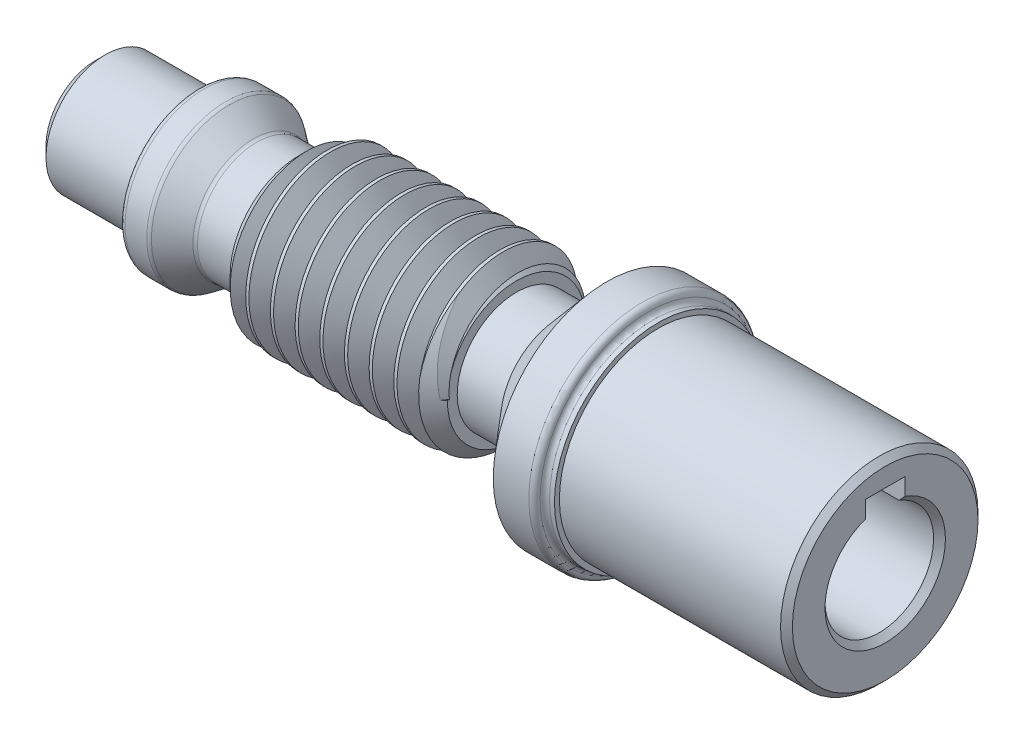
SolidWorks part; units mm, degrees
ref_plane "Horní rovina" through (0, 0, 0) normal (0, 0, 1) x (1, 0, 0)
ref_plane "Přední rovina" through (0, 0, 0) normal (0, 1, 0) x (1, 0, 0)
ref_plane "Pravá rovina" through (0, 0, 0) normal (1, 0, 0) x (0, 0, -1)
sketch "Skica1" plane through (0, 0, 0) normal (0, 0, 1) x (1, 0, 0)
  line L0 (-66.8729, 0) -> (68.6178, 0) construction
  line L1 (-40, 0) -> (40, 0)
  line L2 (40, 0) -> (40, 10)
  line L3 (40, 10) -> (17, 10)
  line L4 (17, 10) -> (17, 10.5)
  line L5 (17, 10.5) -> (16.5, 10.5)
  line L6 (16, 11) -> (16, 11.5)
  line L7 (16, 11.5) -> (11.8, 11.5)
  line L8 (11.8, 11.5) -> (7.05, 6)
  line L9 (7.05, 6) -> (2.65, 6)
  line L10 (2.65, 6) -> (2.65, 7)
  line L11 (1.15, 8.5) -> (-17.85, 8.5)
  line L12 (-19.35, 7) -> (-19.35, 6)
  line L13 (-19.35, 6) -> (-23.85, 6)
  line L14 (-23.85, 6) -> (-26.6, 8)
  line L15 (-26.6, 8) -> (-29.6, 8)
  line L16 (-40, 0) -> (-40, 6)
  line L17 (-40, 6) -> (-30.6, 6)
  line L18 (-29.6, 8) -> (-29.6, 6)
  line L19 (-17.85, 8.5) -> (-19.35, 7)
  line L20 (2.65, 7) -> (1.15, 8.5)
  arc A0 (-30.6, 6) -> (-29.6, 6) centre (-30.1, 6) ccw
  arc A1 (16.5, 10.5) -> (16, 11) centre (16.5, 11) cw
  point P6 (0, 0)
  point P13 (2.65, 8.5)
  point P16 (-19.35, 8.5)
  point P27 (16, 10.5)
  point P28 (17, 10.25)
  dimension "D4" = 0.5
  dimension "D20" = 0.5
  dimension "D22" = 0.5
  dimension "D1" = 80
  dimension "D2" = 10
  dimension "D3" = 23
  dimension "D5" = 24
  dimension "D6" = 1
  dimension "D7" = 4.2
  dimension "D8" = 4.4
  dimension "D9" = 22
  dimension "D10" = 4.5
  dimension "D11" = 46.6
  dimension "D12" = 4.75
  dimension "D13" = 6
  dimension "D14" = 8.5
  dimension "D15" = 6
  dimension "D16" = 8
  dimension "D17" = 3
  dimension "D18" = 6
  dimension "D21" = 2
  dimension "D23" = 10.4
revolve "Rotovat1" add sketch "Skica1" angle 360 about L0
chamfer "Zkosení1" distance 0.6 angle 45 1 edges at (40, 0, 10)
fillet "Zaoblit1" radius 0.6 4 edges at (-29.6, 0, 8) (-23.85, 0, 6) (-26.6, 0, 8) (16, 0, 11.5)
chamfer "Zkosení2" distance 1 angle 45 1 edges at (-40, 0, 6)
sketch "Skica2" plane through (40, 0, 0) normal (1, 0, 0) x (0, 0, -1)
  line L0 (0, 7.7019) -> (0, -6.0718) construction
  line L1 (-3.8348, -5.5) -> (3.7867, -5.5) construction
  line L2 (-2, 7.5) -> (2, 7.5)
  line L3 (-2, 7.5) -> (-2, 5.1235)
  line L5 (2, 7.5) -> (2, 5.1235)
  arc A0 (-2, 5.1235) -> (2, 5.1235) centre (0, 0) ccw
  point P6 (0, 5.845)
  dimension "D1" = 11
  dimension "D2" = 13
  dimension "D3" = 4
extrude "Odebrat vysunutím1" cut sketch "Skica2" against normal blind 29
chamfer "Zkosení3" distance 0.6 angle 45 1 edges at (40, -5.5, 0)
sketch "Skica3" plane through (-40, 0, 0) normal (-1, 0, 0) x (0, 0, 1)
  circle A0 centre (0, 0) radius 2.25
  dimension "D1" = 4.5
extrude "Odebrat vysunutím2" cut sketch "Skica3" against normal blind 3 draft 32.5
sketch "Skica4" plane through (2.65, 0, 0) normal (1, 0, 0) x (0, 0, -1)
  circle A0 centre (0, 0) radius 8.5 construction
  circle A1 centre (0, 0) radius 8.5
curve "Šroubovice/spirála1" pitch 2.5 height 22 turns 8.8
sketch "Skica5" plane through (0, 0, 0) normal (0, 1, 0) x (1, 0, 0)
  line L0 (1.55, -8.52) -> (3.75, -8.52)
  line L1 (3.75, -8.52) -> (2.65, -6.8)
  line L2 (2.65, -6.8) -> (1.55, -8.52)
  line L3 (2.65, -6.8) -> (2.65, -8.52) construction
  line L4 (0, 0) -> (6.5533, 0) construction
  point P5 (2.65, -8.5)
  dimension "D1" = 2.2
  dimension "D2" = 6.8
  dimension "D3" = 0.02
sweep "Odebrat tažením po křivce1" cut profiles "Skica5" path "Šroubovice/spirála1"
